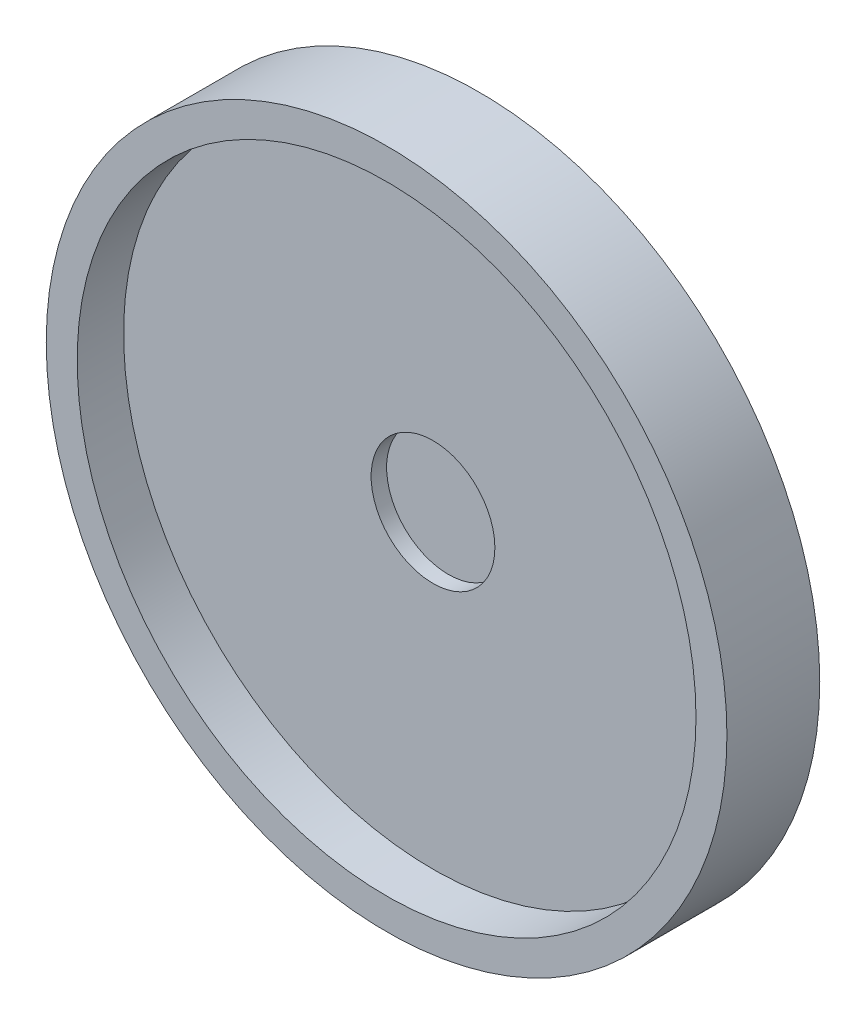
SolidWorks part; units mm, degrees
ref_plane "Plano frontal" through (0, 0, 0) normal (0, 0, 1) x (1, 0, 0)
ref_plane "Plano superior" through (0, 0, 0) normal (0, 1, 0) x (1, 0, 0)
ref_plane "Plano direito" through (0, 0, 0) normal (1, 0, 0) x (0, 0, -1)
sketch "Esboço1" plane through (0, 0, 0) normal (0, 0, 1) x (1, 0, 0)
  circle A0 centre (0, 0) radius 20
  circle A1 centre (0, 0) radius 4
  circle A2 centre (0, 0) radius 22
  dimension "D1" = 40
  dimension "D2" = 8
  dimension "D3" = 2
extrude "Ressalto-extrusão3" add sketch "Esboço1" along normal blind 3 contours A0 A1 region at (-19.4343, 0, 0)
extrude "Ressalto-extrusão4" add sketch "Esboço1<6>" along normal blind 6 contours A2 A0 region at (-21.3777, 0, 0)
sketch "Esboço1<6>" plane through (0, 0, 0) normal (0, 0, 1) x (1, 0, 0) same geometry as "Esboço1"
extrude "Ressalto-extrusão5" add sketch "Esboço1<7>" along normal blind 2 contours A1 region at (0, 0, 0)
sketch "Esboço1<7>" plane through (0, 0, 0) normal (0, 0, 1) x (1, 0, 0) same geometry as "Esboço1"
